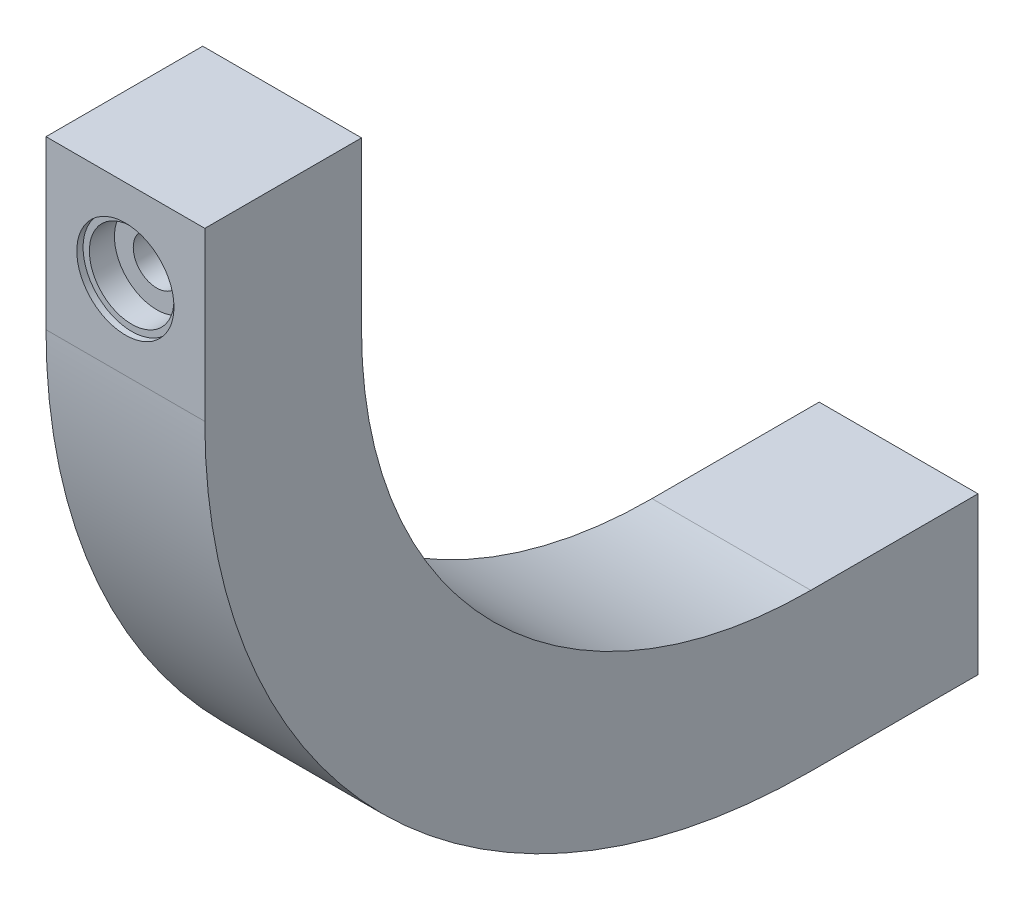
SolidWorks part; units mm, degrees
ref_plane "Front Plane" through (0, 0, 0) normal (0, 0, 1) x (1, 0, 0)
ref_plane "Top Plane" through (0, 0, 0) normal (0, 1, 0) x (1, 0, 0)
ref_plane "Right Plane" through (0, 0, 0) normal (1, 0, 0) x (0, 0, -1)
ref_axis "Z" through (0, 0, 109.5585) along (0, 0, -1)
ref_axis "X" through (8.36, 0, 0) along (-1, 0, 0)
sketch "Sketch4" plane through (0, 0, 0) normal (0, 0, 1) x (1, 0, 0)
  circle A0 centre (0, 0) radius 50 construction
  dimension "D1" = 100
sketch "Sketch5" plane through (0, 0, 0) normal (1, 0, 0) x (0, 0, -1)
  line L0 (-51, 8) -> (-51, 0)
  line L1 (-51, 0) -> (-51, -8)
  line L2 (-66, -8) -> (-66, 8)
  line L6 (-66, 8) -> (-51, 8)
  line L12 (-109.5585, 0) -> (-13.0351, 0) construction
  line L13 (0, 0) -> (-14.9091, -14.9091) construction
  line L14 (0, 0) -> (7.0065, 0) construction
  line L15 (0, -51) -> (-8, -51)
  line L16 (8, -51) -> (0, -51)
  line L17 (-8, -66) -> (8, -66)
  line L18 (8, -66) -> (8, -51)
  circle A0 centre (0, 0) radius 14 construction
  arc A1 (-51, -8) -> (-8, -51) centre (-8, -8) ccw
  arc A2 (-66, -8) -> (-8, -66) centre (-8, -8) ccw
  point P2 (9.4307, -21)
  point P4 (0, -2.1363)
  dimension "D1" = 28
  dimension "D4" = 8
  dimension "D2" = 45
  dimension "D3" = 15
  dimension "D5" = 51
sketch "Sketch6" plane through (0, 0, 0) normal (0, 1, 0) x (1, 0, 0)
  circle A0 centre (0, 0) radius 50 construction
  dimension "D1" = 100
extrude "Boss-Extrude1" add sketch "Sketch5" along normal blind 7.6 and the other way blind 7.6
sketch "Sketch7" plane through (0, 0, 0) normal (0, 0, 1) x (1, 0, 0)
  circle A0 centre (0, 0) radius 2.25
  dimension "D1" = 4.5
extrude "Cut-Extrude1" cut sketch "Sketch7" along normal through all
ref_axis "Y" through (0, -9.3489, 0) along (0, -1, 0)
sketch "Sketch16" plane through (0, 0, 0) normal (1, 0, 0) x (0, 0, -1)
  line L0 (0, -67) -> (0, 0) construction
  dimension "D1" = 67
ref_plane "Plane1" through (0, -67, 0) normal (0, 1, 0) x (1, 0, 0)
ref_axis "CX" through (0, -67, 4.4) along (0, 0, -1)
ref_plane "Plane2" through (0, 0, 0) normal (0, 0, -1) x (0, 1, 0)
ref_plane "Plane3" through (0, 0, 0) normal (1, 0, 0) x (0, 0, -1)
ref_axis "CZ" through (0, -8.7018, 0) along (0, -1, 0)
ref_axis "CY" through (-0.6471, -67, 0) along (1, 0, 0)
ref_point "CO"
sketch "Sketch15" plane through (0, -66, 0) normal (0, -1, 0) x (1, 0, 0)
  circle A0 centre (0, 0) radius 2.05
  dimension "D1" = 4.1
extrude "Cut-Extrude11" cut sketch "Sketch15" against normal blind 10
sketch "Sketch18" plane through (0, 0, 0) normal (1, 0, 0) x (0, 0, -1)
  line L0 (-66, 4.65) -> (-66, 0)
  line L1 (-66, 0) -> (-63, 0)
  line L2 (-63, 0) -> (-63, 4.05)
  line L3 (-63, 4.05) -> (-65.4, 4.05)
  line L4 (-65.4, 4.05) -> (-65.4, 4.65)
  line L5 (-65.4, 4.65) -> (-66, 4.65)
  line L6 (-68.6876, 0) -> (-58.5, 0) construction
  line L7 (-58.5, 0) -> (-58.5, 8) construction
  line L8 (-51.6, 4.65) -> (-51, 4.65)
  line L9 (-51.6, 4.05) -> (-51.6, 4.65)
  line L10 (-54, 4.05) -> (-51.6, 4.05)
  line L11 (-54, 0) -> (-54, 4.05)
  line L12 (-51, 0) -> (-54, 0)
  line L13 (-51, 4.65) -> (-51, 0)
  line L14 (-109.5585, 0) -> (-13.0351, 0) construction
  line L15 (-66, 8) -> (-51, 8) construction
  line L16 (-66, -8) -> (-66, 8) construction
  dimension "D1" = 0.6
  dimension "D2" = 8.1
  dimension "D3" = 3
  dimension "D4" = 4.65
revolve "Cut-Revolve1" cut sketch "Sketch18" angle 360 about axis through (0, 0, 109.5585) along (0, 0, -1)
equation "\"rbracket-width\"= \"L2Thickness\" + 0.2"
equation "\"EyeCaptureRadius\"= ( \"EyeDiameter\" + \"EyeClearance\" ) / 2"
equation "\"rbracket_planetocenterline_dist\"= \"BasePlaneDistance\""
equation "\"EyeDiameter\" = 100"
equation "\"BasePlaneDistance\" = \"EyeDiameter\"/2+\"L2Thickness\"+\"EyeClearance\""
equation "\"EyeClearance\" = 2"
equation "\"D1@Sketch4\"=\"EyeDiameter\""
equation "\"D1@Sketch6\"=\"EyeDiameter\""
equation "\"D1@Boss-Extrude1\"=\"rbracket-width\"/2"
equation "\"D2@Boss-Extrude1\"=\"rbracket-width\"/2"
equation "\"L2Thickness\" = 3.75 * \"shaft_diameter\""
equation "\"D3@Sketch5\"=\"L2Thickness\""
equation "\"D5@Sketch5\"=(\"EyeDiameter\"+\"EyeClearance\")/2"
equation "\"BearingThickness\"= 6"
equation "\"BearingOD\"=4.5"
equation "\"OuterBearingProudDistance\"= 0"
equation "\"FlangeOD\"=7.5"
equation "\"FlangeThickness\"= 0.75"
equation "\"PrinterFilamentThickness\"= 0.1'For setting distances for things like pressfits"
equation "\"ApplyPrinterOffset\"= 1'Set to 0 for line-to-line. Set to 1 for applying guestimate dimensions to make the printer produce good parts"
equation "\"D1@Cut-Extrude11\"=\"shaft_diameter\"*2.5"
equation "\"D1@Sketch16\"=\"BasePlaneDistance\""
equation "\"D2@Sketch18\"=\"ApplyPrinterOffset\"*\"PrinterFilamentThickness\" + 8"
equation "\"D4@Sketch18\"=4.6 + \"ApplyPrinterOffset\"*\"PrinterFilamentThickness\"/2"
equation "\"L2_ID\" = 20"
equation "\"vx\" = 0"
equation "\"vy\" = 0"
equation "\"vz\" = 100"
equation "\"parametric_end\" = 1"
equation "\"Rw_3_xx\" = -(\"vz\")/sqr((\"vx\")^2 + (\"vz\")^2)"
equation "\"Rw_3_xy\" = 0"
equation "\"Rw_3_xz\" = (\"vx\")/sqr((\"vx\")^2 + (\"vz\")^2)"
equation "\"Rw_3_zx\" = (\"vx\")/sqr((\"vx\")^2 + (\"vy\")^2 + (\"vz\")^2)"
equation "\"Rw_3_zy\" = (\"vy\")/sqr((\"vx\")^2 + (\"vy\")^2 + (\"vz\")^2)"
equation "\"Rw_3_zz\" = (\"vz\")/sqr((\"vx\")^2 + (\"vy\")^2 + (\"vz\")^2)"
equation "\"Rw_3_yx\" = (\"vx\")*(\"vy\")/sqr((\"vx\")^4 + (\"vx\")^2*(\"vy\")^2 + 2*(\"vx\")^2*(\"vz\")^2 + (\"vy\")^2*(\"vz\")^2 + (\"vz\")^4)"
equation "\"Rw_3_yy\" = -sqr((\"vx\")^2 + (\"vz\")^2)/sqr((\"vx\")^2 + (\"vy\")^2 + (\"vz\")^2)"
equation "\"Rw_3_yz\" = (\"vy\")*(\"vz\")/sqr((\"vx\")^4 + (\"vx\")^2*(\"vy\")^2 + 2*(\"vx\")^2*(\"vz\")^2 + (\"vy\")^2*(\"vz\")^2 + (\"vz\")^4)"
equation "\"O2Targx\" = -\"BasePlaneDistance\"*(\"vx\")*(\"vy\")/sqr((\"vx\")^4 + (\"vx\")^2*(\"vy\")^2 + 2*(\"vx\")^2*(\"vz\")^2 + (\"vy\")^2*(\"vz\")^2 + (\"vz\")^4)"
equation "\"O2Targy\" = \"BasePlaneDistance\"*sqr((\"vx\")^2 + (\"vz\")^2)/sqr((\"vx\")^2 + (\"vy\")^2 + (\"vz\")^2)"
equation "\"O2Targz\" = -\"BasePlaneDistance\"*(\"vy\")*(\"vz\")/sqr((\"vx\")^4 + (\"vx\")^2*(\"vy\")^2 + 2*(\"vx\")^2*(\"vz\")^2 + (\"vy\")^2*(\"vz\")^2 + (\"vz\")^4)"
equation "\"O2Targx_0\" = -(\"BasePlaneDistance\")*sqr((\"vx\")^2 + (\"vz\")^2)/sqr((\"vx\")^2 + (\"vy\")^2 + (\"vz\")^2)"
equation "\"O2Targy_0\" = -(\"BasePlaneDistance\")*(\"vy\")*(\"vz\")/sqr((\"vx\")^4 + (\"vx\")^2*(\"vy\")^2 + 2*(\"vx\")^2*(\"vz\")^2 + (\"vy\")^2*(\"vz\")^2 + (\"vz\")^4)"
equation "\"O2Targz_0\" = (\"BasePlaneDistance\")*(\"vx\")*(\"vy\")/sqr((\"vx\")^4 + (\"vx\")^2*(\"vy\")^2 + 2*(\"vx\")^2*(\"vz\")^2 + (\"vy\")^2*(\"vz\")^2 + (\"vz\")^4) + (\"BasePlaneDistance\")"
equation "\"theta2_s1\" = arcsin(((\"BasePlaneDistance\") - (\"O2Targz_0\"))/(\"BasePlaneDistance\")) + pi"
equation "\"theta2_s2\" = -arcsin(((\"BasePlaneDistance\") - (\"O2Targz_0\"))/(\"BasePlaneDistance\"))"
equation "\"theta1_s1\" = arcsin((\"O2Targy_0\")/((\"BasePlaneDistance\")*cos((\"Theta2\")))) + pi"
equation "\"theta1_s2\" = -arcsin((\"O2Targy_0\")/((\"BasePlaneDistance\")*cos((\"Theta2\"))))"
equation "\"theta1_s3\" = -arccos(-(\"O2Targx_0\")/((\"BasePlaneDistance\")*cos((\"Theta2\")))) + 2*pi"
equation "\"theta1_s4\" = arccos(-(\"O2Targx_0\")/((\"BasePlaneDistance\")*cos((\"Theta2\"))))"
equation "\"Theta1\" = \"theta1_s2\" 'so far, theta1_s1 and theta1_s4 have agreed, and they agree with the sw constraint solver"
equation "\"Theta2\" = \"theta2_s2\""
equation "\"o2_x\" = -(\"BasePlaneDistance\")*cos((\"Theta1\"))*cos((\"Theta2\"))"
equation "\"o2_y\" = -(\"BasePlaneDistance\")*sin((\"Theta1\"))*cos((\"Theta2\"))"
equation "\"o2_z\" = (\"BasePlaneDistance\")*(sin((\"Theta2\")) + 1)"
equation "\"o1_x\" = (\"BasePlaneDistance\")*sin((\"Theta1\"))"
equation "\"o1_y\" = -(\"BasePlaneDistance\")*cos((\"Theta1\"))"
equation "\"o1_z\" = (\"BasePlaneDistance\")"
equation "\"Actuator1_Theta\" = atn(\"vx\"/\"vz\") 'ik solution for the single link joint"
equation "\"Actuator2_Theta\" = \"Theta1\"  'ik solution for the double link joint"
equation "\"MotorBaseThickness\" = 3 "
equation "\"BaseThickness\" = 3 "
equation "\"EncoderToMagnetAirgap\" = 1 'Encoder to magnet airgap"
equation "\"EncoderHeight\" = 1.192  'Height of the encoder"
equation "\"MagnetThickness\" = 0.5  'Magnet thickness"
equation "\"pcb_thickness\" = 1.6  'Thickness of the PCB"
equation "\"pcb_outer_diameter\" = 32 'the OD of the pcb"
equation "\"shaft_diameter\" = 4"
equation "\"D1@Sketch15\"=\"shaft_diameter\"+\"ApplyPrinterOffset\"*\"PrinterFilamentThickness\""
